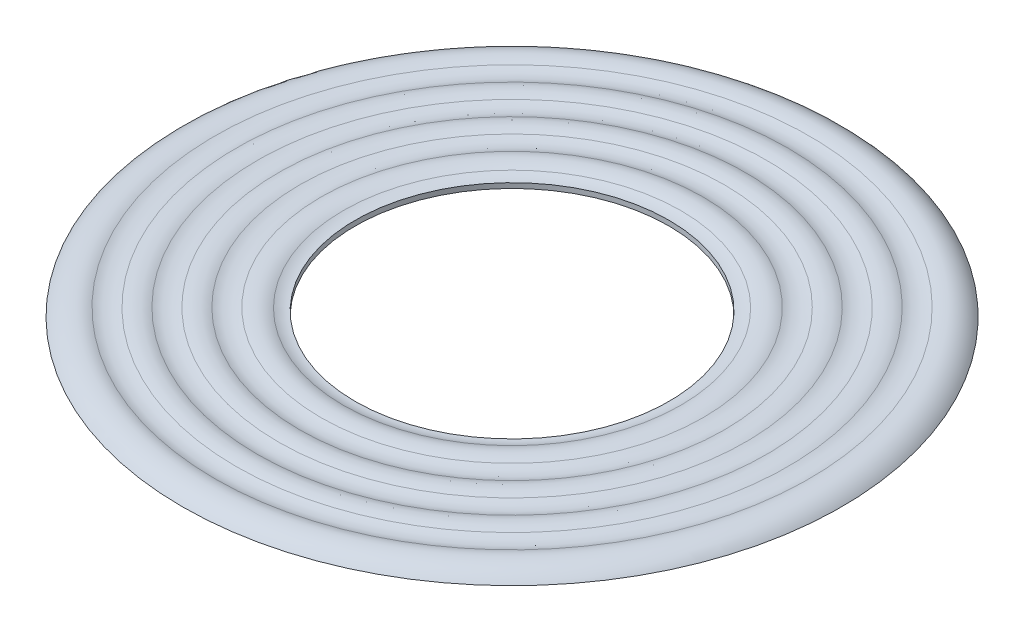
SolidWorks part; units mm, degrees
material "Copper"
ref_plane "Front Plane" through (0, 0, 0) normal (0, 0, 1) x (1, 0, 0)
ref_plane "Top Plane" through (0, 0, 0) normal (0, 1, 0) x (1, 0, 0)
ref_plane "Right Plane" through (0, 0, 0) normal (1, 0, 0) x (0, 0, -1)
sketch "sketch0" plane through (0, 0, 0) normal (0, 0, 1) x (1, 0, 0)
  line L0 (0, 35.6539) -> (0, -35.906) construction
  line L1 (-33.3375, 0.508) -> (-15.875, 0.508)
  line L2 (-33.3375, 0.508) -> (-33.3375, -0.508)
  line L3 (-33.3375, -0.508) -> (-15.875, -0.508)
  line L4 (-15.875, 0.508) -> (-15.875, -0.508)
  line L5 (-33.3375, 0) -> (0, 0) construction
  dimension "OD" = 66.675
sketch "Sketch1" plane through (0, 0, 0) normal (0, 0, 1) x (1, 0, 0)
  line L0 (-15.875, 0) -> (0, 0) construction
  line L1 (-33.3375, 0) -> (-15.875, 0) construction
  line L2 (0, 27.311) -> (0, -23.1526) construction
  line L3 (-33.3375, -0.508) -> (-15.875, -0.508)
  line L4 (-15.875, -0.508) -> (-15.875, 0)
  line L5 (-15.875, 0.508) -> (-15.875, -0.508) construction
  line L8 (-33.3375, 0.508) -> (-33.3375, -0.508) construction
  line L9 (-33.3375, 0.508) -> (-15.875, 0.508) construction
  line L11 (-33.3375, 0.1016) -> (-36.8709, 0.1016) construction
  line L12 (-33.3375, -0.508) -> (-15.875, -0.508) construction
  arc A0 (-30.0486, 0.3048) -> (-27.9053, 0.3048) centre (-28.9769, 3.029) ccw
  arc A1 (-27.9053, 0.3048) -> (-25.762, 0.3048) centre (-26.8336, -2.4194) cw
  arc A2 (-25.762, 0.3048) -> (-23.6187, 0.3048) centre (-24.6904, 3.029) ccw
  arc A3 (-23.6187, 0.3048) -> (-21.4754, 0.3048) centre (-22.5471, -2.4194) cw
  arc A4 (-21.4754, 0.3048) -> (-19.3321, 0.3048) centre (-20.4038, 3.029) ccw
  arc A5 (-19.3321, 0.3048) -> (-17.0677, 0.254) centre (-18.2605, -2.4194) cw
  arc A6 (-17.0677, 0.254) -> (-15.875, 0) centre (-15.875, 2.9274) ccw
  arc A7 (-33.3375, -0.508) -> (-30.0486, 0.3048) centre (-31.1202, -2.4194) cw
  point P22 (-50.4404, 0.1016)
  dimension "D1" = 0.6096
revolve "Revolve1" add sketch "Sketch1" angle 360 about L2
shell "Shell1" thickness 0.6096 removed face at (0, -0.508, 15.875)
equation "\"D1@Sketch1\"=\"Thick@sketch0\"*.6"
equation "\"D1@Shell1\"=\"D1@Sketch1\"*1"
